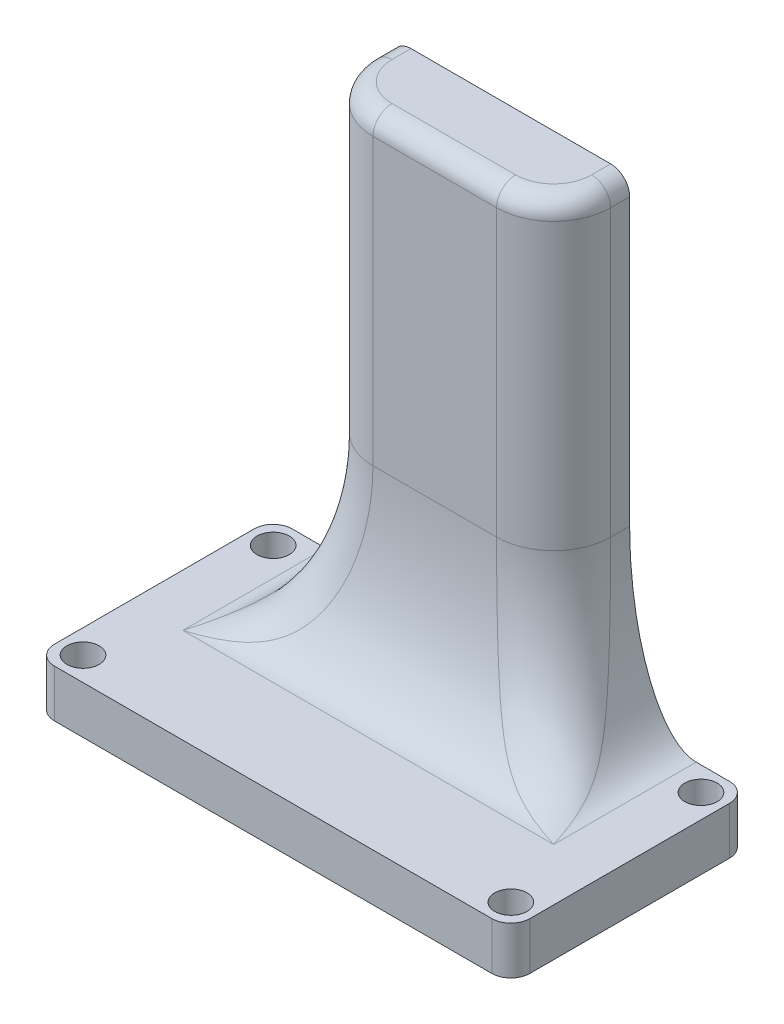
SolidWorks part; units mm, degrees
ref_plane "Front Plane" through (0, 0, 0) normal (0, 0, 1) x (1, 0, 0)
ref_plane "Top Plane" through (0, 0, 0) normal (0, 1, 0) x (1, 0, 0)
ref_plane "Right Plane" through (0, 0, 0) normal (1, 0, 0) x (0, 0, -1)
sketch "Sketch1" plane through (0, 0, 0) normal (0, 1, 0) x (1, 0, 0)
  line L1 (-25, -12.5) -> (25, -12.5)
  line L2 (-25, -12.5) -> (-25, 12.5)
  line L3 (-25, 12.5) -> (25, 12.5)
  line L4 (25, -12.5) -> (25, 12.5)
  line L5 (-25, -12.5) -> (25, 12.5) construction
  line L6 (-25, 12.5) -> (25, -12.5) construction
  line L7 (22.5, -10) -> (-22.5, -10) construction
  line L8 (22.5, -10) -> (22.5, 10) construction
  line L9 (22.5, 10) -> (-22.5, 10) construction
  line L10 (-22.5, -10) -> (-22.5, 10) construction
  line L11 (22.5, -10) -> (-22.5, 10) construction
  line L12 (22.5, 10) -> (-22.5, -10) construction
  circle A0 centre (-22.5, 10) radius 1.7
  circle A1 centre (22.5, 10) radius 1.7
  circle A2 centre (22.5, -10) radius 1.7
  circle A3 centre (-22.5, -10) radius 1.7
  point P0 (0, 0)
  point P6 (0, 0)
  dimension "D3" = 3.4
  dimension "D4" = 3.4
  dimension "D5" = 3.4
  dimension "D6" = 3.4
  dimension "D1" = 50
  dimension "D2" = 25
  dimension "D7" = 20
  dimension "D8" = 45
extrude "Boss-Extrude1" add sketch "Sketch1" along normal blind 5 contours L1 L4 L3 L2 A3 A2 A1 A0 region at (0, 0, 0)
sketch "Sketch2" plane through (0, 5, 0) normal (0, 1, 0) x (1, 0, 0)
  line L1 (-12.5, 4.5) -> (12.5, 4.5)
  line L2 (-12.5, 4.5) -> (-12.5, 12.5)
  line L3 (-12.5, 12.5) -> (12.5, 12.5)
  line L4 (12.5, 4.5) -> (12.5, 12.5)
  line L5 (-12.5, 4.5) -> (12.5, 12.5) construction
  line L6 (-12.5, 12.5) -> (12.5, 4.5) construction
  line L9 (-25, 12.5) -> (25, 12.5) construction
  point P0 (0, 8.5)
  dimension "D1" = 8
  dimension "D2" = 25
extrude "Boss-Extrude2" add sketch "Sketch2" along normal blind 50
fillet "Fillet1" radius 7 3 edges at (12.5, 5, -8.5) (-12.5, 5, -8.5) (0, 5, -4.5) second distance 18 first distance on face at (0, 5, -4.25)
fillet "Fillet2" radius 6 4 edges
fillet "Fillet3" radius 2 5 edges at (10.7426, 55, -6.2574) (0, 55, -4.5) (-10.7426, 55, -6.2574) (-12.5, 55, -11.5) (12.5, 55, -11.5)
fillet "Fillet4" radius 2 4 edges at (25, 2.5, -12.5) (25, 2.5, 12.5) (-25, 2.5, 12.5) (-25, 2.5, -12.5)
